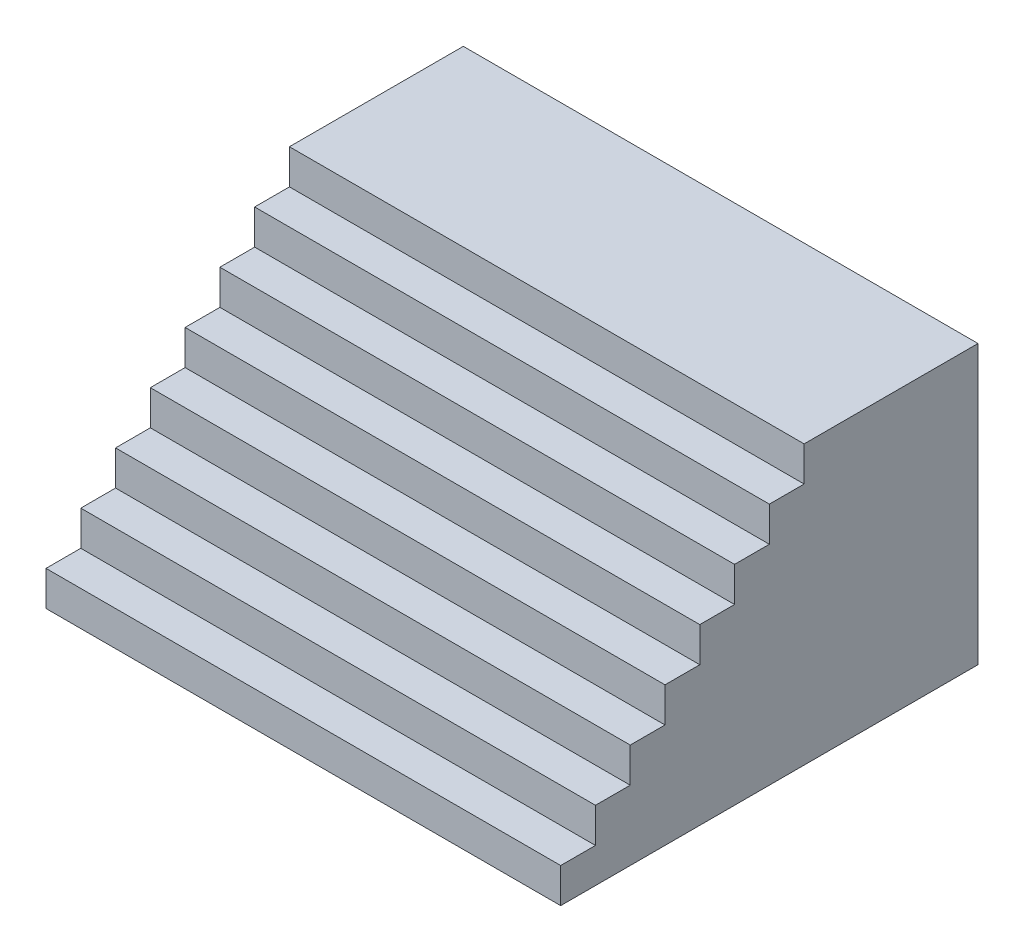
SolidWorks part; units mm, degrees
material "Alloy Steel"
ref_plane "Front Plane" through (0, 0, 0) normal (0, 0, 1) x (1, 0, 0)
ref_plane "Top Plane" through (0, 0, 0) normal (0, 1, 0) x (1, 0, 0)
ref_plane "Right Plane" through (0, 0, 0) normal (1, 0, 0) x (0, 0, -1)
sketch3d "3DSketch1"
  line L4 (1850, -1000, 0) -> (1850, 1000, 0)
  line L5 (1850, -1000, 0) -> (-1850, -1000, 0) construction
  line L6 (-1850, -1000, 0) -> (-1850, 1000, 0) construction
  line L7 (1850, -1000, 0) -> (1850, -1000, 3000)
  line L9 (1850, -1000, 3000) -> (1850, -750, 3000)
  line L10 (1850, -750, 3000) -> (1850, -750, 2750)
  line L11 (1850, -750, 2750) -> (1850, -500, 2750)
  line L12 (1850, -500, 2750) -> (1850, -500, 2500)
  line L13 (1850, -500, 2500) -> (1850, -250, 2500)
  line L14 (1850, -250, 2500) -> (1850, -250, 2250)
  line L15 (1850, -250, 2250) -> (1850, 0, 2250)
  line L16 (1850, 0, 2250) -> (1850, 0, 2000)
  line L17 (1850, 0, 2000) -> (1850, 250, 2000)
  line L18 (1850, 250, 2000) -> (1850, 250, 1750)
  line L19 (1850, 250, 1750) -> (1850, 500, 1750)
  line L20 (1850, 500, 1750) -> (1850, 500, 1500)
  line L21 (1850, 500, 1500) -> (1850, 750, 1500)
  line L22 (1850, 750, 1500) -> (1850, 750, 1250)
  line L23 (1850, 750, 1250) -> (1850, 1000, 1250)
  line L24 (1850, 1000, 1250) -> (1850, 1000, 0)
  line L41 (1850, 1000, 0) -> (-1850, 1000, 0) construction
  line L43 (-1850, -1000, 0) -> (-1850, -1000, 3000) construction
  line L44 (1850, -1000, 3000) -> (-1850, -1000, 3000) construction
  point P0 (0, 0, 0)
  dimension "D20" = 3000
  dimension "D2" = 3700
  dimension "D3" = 3000
  dimension "D4" = 2000
  dimension "D5" = 250
  dimension "D6" = 250
  dimension "D7" = 250
  dimension "D8" = 250
  dimension "D9" = 250
  dimension "D10" = 250
  dimension "D11" = 250
  dimension "D12" = 250
  dimension "D13" = 250
  dimension "D14" = 250
  dimension "D15" = 250
  dimension "D16" = 250
  dimension "D17" = 250
  dimension "D18" = 250
  dimension "D19" = 250
extrude "Boss-Extrude2" add sketch "3DSketch1" along direction (-1, 0, 0) on the side of the normal blind 3700 contours L7 L9 L10 L11 L12 L13 L14 L15 L16 L17 L18 L19 L20 L21 L22 L23 L24 L4
